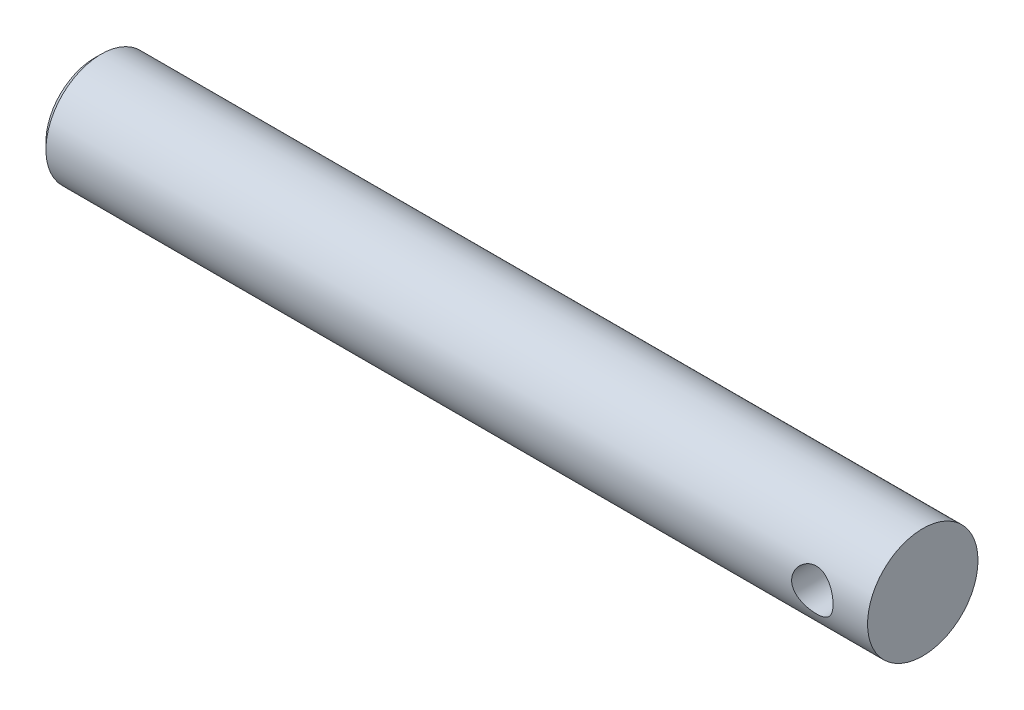
SolidWorks part; units mm, degrees
material "PW20:22:Sc:0:"
ref_plane "front" through (0, 0, 0) normal (0, 0, 1) x (1, 0, 0)
ref_plane "top" through (0, 0, 0) normal (0, 1, 0) x (1, 0, 0)
ref_plane "side" through (0, 0, 0) normal (1, 0, 0) x (0, 0, -1)
other "Configuration Table"
sketch "Sketch1" plane through (0, 0, 0) normal (1, 0, 0) x (0, 0, -1)
  circle A0 centre (0, 0) radius 6.35
  dimension "D1" = 12.7
extrude "Base-Extrude" add sketch "Sketch1" along normal blind 95.25
sketch "Sketch2" plane through (0, 0, 0) normal (0, 0, 1) x (1, 0, 0)
  line L0 (95.25, 6.35) -> (95.25, -6.35) construction
  line L1 (50, 0) -> (-50, 0) construction
  circle A0 centre (88.9, 0) radius 2.3813
  dimension "D2" = 4.7625
  dimension "D1" = 6.35
extrude "Cut-Extrude1" cut sketch "Sketch2" against normal through all and the other way through all
sketch "Sketch3" plane through (0, 0, 0) normal (-1, 0, 0) x (0, 0, 1)
  circle A0 centre (0, 0) radius 2.3813
  dimension "D1" = 4.7625
extrude "Cut-Extrude2" cut sketch "Sketch3" against normal blind 25.4
chamfer "Chamfer2" distance 0.762 angle 45 1 edges at (0, 0, -6.35)
ref_axis "Axis1" through (145.25, 0, 0) along (-1, 0, 0)
